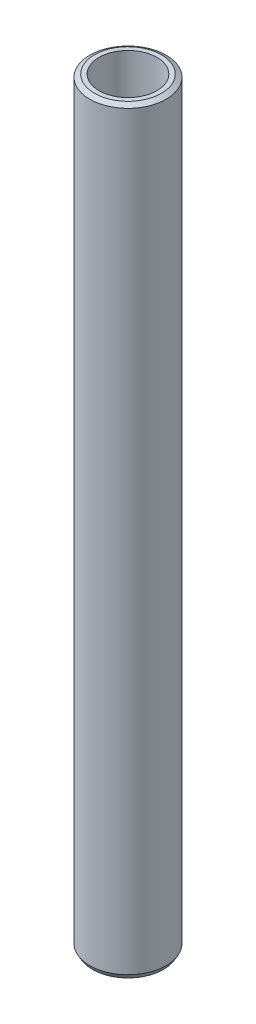
SolidWorks part; units mm, degrees
ref_plane "Front Plane" through (0, 0, 0) normal (0, 0, 1) x (1, 0, 0)
ref_plane "Top Plane" through (0, 0, 0) normal (0, 1, 0) x (1, 0, 0)
ref_plane "Right Plane" through (0, 0, 0) normal (1, 0, 0) x (0, 0, -1)
sketch "Sketch1" plane through (0, 0, 0) normal (0, 1, 0) x (1, 0, 0)
  circle A0 centre (0, 0) radius 27.5
  dimension "SHAFT_OD" = 55
extrude "Boss-Extrude1" add sketch "Sketch1" along normal blind 545.6138
sketch "Sketch2" plane through (0, 0, 0) normal (0, 1, 0) x (1, 0, 0)
  circle A0 centre (0, 0) radius 20.8105
  dimension "BORE_D" = 41.6211
extrude "Cut-Extrude1" cut sketch "Sketch2" along normal through all
chamfer "Chamfer1" distance 1.9712 angle 60 2 edges at (0, 545.6138, 27.5) (0, 0, 27.5) first distance on face at (0, 545.6138, 27.5) first distance on face at (0, 0, 20.8105)
